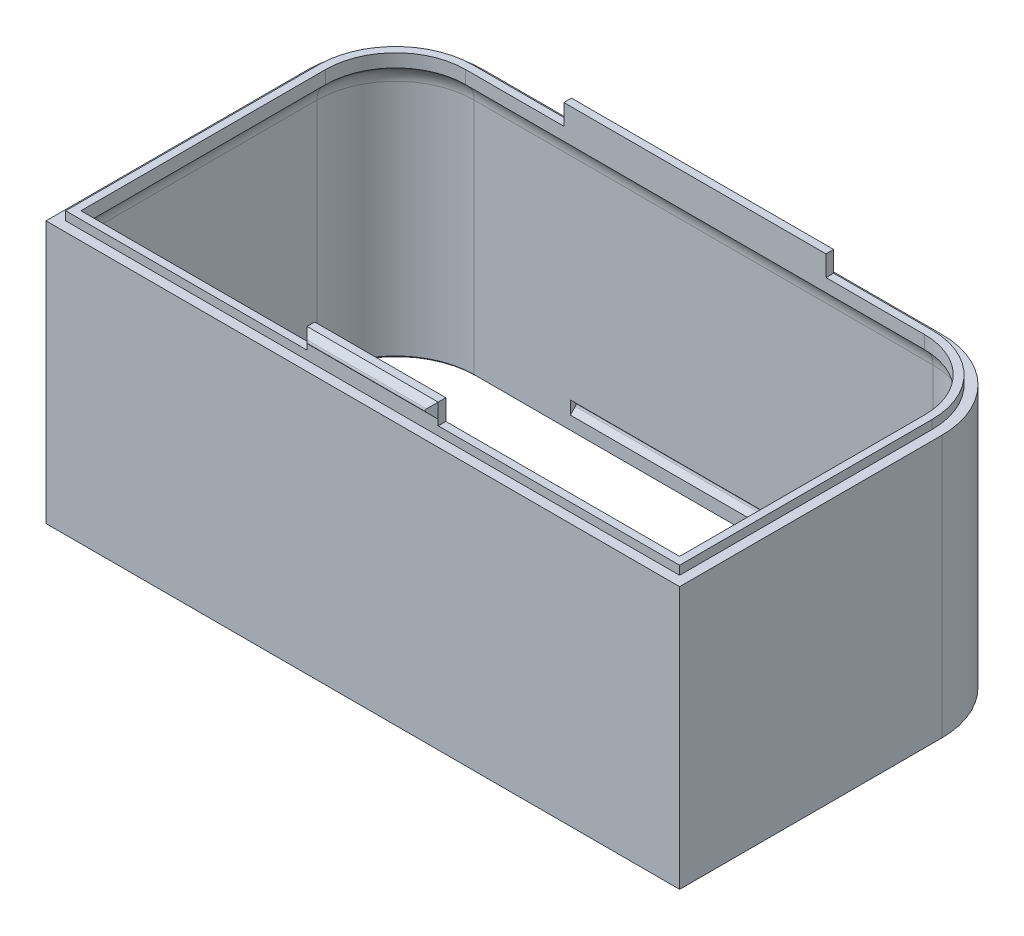
SolidWorks part; units mm, degrees
material "ПК/АБС"
ref_plane "Спереди" through (0, 0, 0) normal (0, 0, 1) x (1, 0, 0)
ref_plane "Сверху" through (0, 0, 0) normal (0, 1, 0) x (1, 0, 0)
ref_plane "Справа" through (0, 0, 0) normal (1, 0, 0) x (0, 0, -1)
sketch "Эскиз1" plane through (0, 0, 0) normal (0, 1, 0) x (1, 0, 0)
  line L0 (-70.5, 2) -> (70.5, 2)
  line L1 (-72.5, 0) -> (72.5, 0)
  line L2 (-72.5, 0) -> (-72.5, 60)
  line L3 (-52.5, 80) -> (52.5, 80)
  line L4 (72.5, 0) -> (72.5, 60)
  line L9 (70.5, 2) -> (70.5, 60)
  line L10 (-52.5, 78) -> (52.5, 78)
  line L11 (-70.5, 2) -> (-70.5, 60)
  arc A0 (72.5, 60) -> (52.5, 80) centre (52.5, 60) ccw
  arc A1 (-52.5, 80) -> (-72.5, 60) centre (-52.5, 60) ccw
  arc A2 (70.5, 60) -> (52.5, 78) centre (52.5, 60) ccw
  arc A3 (-52.5, 78) -> (-70.5, 60) centre (-52.5, 60) ccw
  point P8 (72.5, 80)
  point P11 (-72.5, 80)
  dimension "D3" = 20
  dimension "D1" = 80
  dimension "D2" = 145
  dimension "D4" = 2
extrude "Бобышка-Вытянуть1" add sketch "Эскиз1" along normal blind 60
sketch "Эскиз2" plane through (0, 60, 0) normal (0, 1, 0) x (1, 0, 0)
  line L0 (-68.5, 60) -> (-68.5, 4)
  line L1 (-68.5, 4) -> (68.5, 4)
  line L2 (68.5, 4) -> (68.5, 60)
  line L3 (52.5, 76) -> (-52.5, 76)
  line L4 (-72.5, 60) -> (-72.5, 0)
  line L5 (-72.5, 0) -> (72.5, 0)
  line L6 (72.5, 0) -> (72.5, 60)
  line L7 (52.5, 80) -> (-52.5, 80)
  line L8 (-72.5, 60) -> (-72.5, 0)
  line L9 (-72.5, 0) -> (72.5, 0)
  line L10 (72.5, 0) -> (72.5, 60)
  line L11 (52.5, 80) -> (-52.5, 80)
  arc A0 (68.5, 60) -> (52.5, 76) centre (52.5, 60) ccw
  arc A1 (-52.5, 76) -> (-68.5, 60) centre (-52.5, 60) ccw
  arc A2 (72.5, 60) -> (52.5, 80) centre (52.5, 60) ccw
  arc A3 (-52.5, 80) -> (-72.5, 60) centre (-52.5, 60) ccw
  arc A4 (72.5, 60) -> (52.5, 80) centre (52.5, 60) ccw
  arc A5 (-52.5, 80) -> (-72.5, 60) centre (-52.5, 60) ccw
  dimension "D1" = 0
  dimension "D2" = 4
extrude "Бобышка-Вытянуть2" add sketch "Эскиз2" against normal blind 1
chamfer "Фаска3" distance 2 angle 45 6 edges at (70.5, 59, -31) (65.2279, 59, -72.7279) (0, 59, -78) (-65.2279, 59, -72.7279) (0, 59, -2) (-70.5, 59, -31)
sketch "Эскиз11" plane through (0, 60, 0) normal (0, 1, 0) x (1, 0, 0)
  line L0 (68.5, 4) -> (68.5, 60) construction
  line L1 (-68.5, 4) -> (68.5, 4) construction
  line L2 (-68.5, 60) -> (-68.5, 4) construction
  line L3 (52.5, 76) -> (-52.5, 76) construction
  line L4 (68.5, 4) -> (68.5, 60)
  line L5 (-68.5, 4) -> (68.5, 4)
  line L6 (-68.5, 60) -> (-68.5, 4)
  line L7 (52.5, 76) -> (-52.5, 76)
  line L8 (70.25, 2.25) -> (70.25, 60)
  line L9 (52.5, 77.75) -> (-52.5, 77.75)
  line L10 (-70.25, 60) -> (-70.25, 2.25)
  line L11 (-70.25, 2.25) -> (70.25, 2.25)
  arc A0 (68.5, 60) -> (52.5, 76) centre (52.5, 60) ccw construction
  arc A1 (-52.5, 76) -> (-68.5, 60) centre (-52.5, 60) ccw construction
  arc A2 (68.5, 60) -> (52.5, 76) centre (52.5, 60) ccw
  arc A3 (-52.5, 76) -> (-68.5, 60) centre (-52.5, 60) ccw
  arc A4 (70.25, 60) -> (52.5, 77.75) centre (52.5, 60) ccw
  arc A5 (-52.5, 77.75) -> (-70.25, 60) centre (-52.5, 60) ccw
  dimension "D1" = 1.75
extrude "Бобышка-Вытянуть8" add sketch "Эскиз11" along normal blind 2
sketch "Эскиз12" plane through (0, 0, 0) normal (1, 0, 0) x (0, 0, -1)
  line L0 (76, 59) -> (76, 62) construction
  line L1 (76, 59) -> (76, 62) construction
  line L2 (76, 62) -> (76, 66.7)
  line L3 (76, 66.7) -> (77.75, 66.7)
  line L4 (77.75, 66.7) -> (79.45, 65)
  line L5 (79.45, 65) -> (77.75, 63.3)
  line L6 (77.75, 63.3) -> (77.75, 62)
  line L7 (77.75, 62) -> (76, 62)
  line L9 (80, 60) -> (60, 60) construction
  dimension "D1" = 1.7
  dimension "D2" = 5
extrude "Бобышка-Вытянуть9" add sketch "Эскиз12" along normal mid plane 60
sketch "Эскиз13" plane through (0, 0, 0) normal (1, 0, 0) x (0, 0, -1)
  line L0 (2.25, 62) -> (2.25, 63.3)
  line L1 (2.25, 63.3) -> (0.55, 65)
  line L2 (0.55, 65) -> (2.25, 66.7)
  line L3 (2.25, 66.7) -> (4, 66.7)
  line L4 (4, 66.7) -> (4, 62)
  line L5 (2.25, 62) -> (60, 62) construction
  line L6 (4, 62) -> (2.25, 62)
  line L7 (4, 59) -> (4, 62) construction
  line L8 (4, 59) -> (4, 62) construction
  line L9 (0, 60) -> (60, 60) construction
  dimension "D1" = 5
  dimension "D2" = 1.7
extrude "Бобышка-Вытянуть10" add sketch "Эскиз13" along normal mid plane 30
sketch "Эскиз15" plane through (0, 0, 0) normal (1, 0, 0) x (0, 0, -1)
  line L0 (2, 3.5) -> (2, 6.5)
  line L1 (2, 6.5) -> (0.5, 5)
  line L2 (0.5, 5) -> (2, 3.5)
  line L3 (0, 60) -> (0, 0) construction
  line L4 (0, 0) -> (60, 0) construction
  dimension "D1" = 2
  dimension "D2" = 1.5
  dimension "D3" = 5
extrude "Вырез-Вытянуть2" cut sketch "Эскиз15" against normal mid plane 31
sketch "Эскиз16" plane through (0, 0, 0) normal (1, 0, 0) x (0, 0, -1)
  line L0 (78, 3.5) -> (78, 6.5)
  line L1 (78, 6.5) -> (79.5, 5)
  line L2 (79.5, 5) -> (78, 3.5)
  line L3 (60, 0) -> (80, 0) construction
  dimension "D1" = 2
  dimension "D2" = 1.5
  dimension "D3" = 5
extrude "Вырез-Вытянуть3" cut sketch "Эскиз16" against normal mid plane 61
chamfer "Фаска6" distance 0.5 angle 45 6 edges at (-70.5, 0, -31) (-65.2279, 0, -72.7279) (0, 0, -78) (65.2279, 0, -72.7279) (0, 0, -2) (70.5, 0, -31)
fillet "Скругление3" radius 5 6 edges at (70.5, 57, -31) (65.2279, 57, -72.7279) (0, 57, -78) (-65.2279, 57, -72.7279) (0, 57, -2) (-70.5, 57, -31)
fillet "Скругление4" radius 0.5 2 edges at (0, 5, -0.5) (0, 5, -79.5)
fillet "Скругление5" radius 0.5 2 edges at (0, 65, -79.45) (0, 65, -0.55)
sketch "Эскиз18" plane through (0, 0, 0) normal (0, 0, 1) x (1, 0, 0)
  line L0 (-72.5, 0) -> (72.5, 0) construction
  line L1 (-11, 30) -> (-10, 30)
  line L2 (-11, 30) -> (-11, 0)
  line L3 (-11, 0) -> (-10, 0)
  line L4 (-10, 30) -> (-10, 0)
  line L5 (-10, 30) -> (10, 30) construction
  line L6 (10, 30) -> (11, 30)
  line L7 (10, 30) -> (10, 0)
  line L8 (10, 0) -> (11, 0)
  line L9 (11, 30) -> (11, 0)
  line L10 (0, 0) -> (0, 30) construction
  dimension "D1" = 20
  dimension "D2" = 1
  dimension "D3" = 30
extrude "Вырез-Вытянуть4" [suppressed] cut sketch "Эскиз18" against normal up to surface (2 mm away) up to face at (0, 5, -2)
sketch "Эскиз19" plane through (0, 62, 0) normal (0, 1, 0) x (1, 0, 0)
  line L0 (30, 77.75) -> (28, 79.75)
  line L2 (28, 79.75) -> (30, 79.75)
  line L4 (30, 79.75) -> (30, 77.75)
  line L5 (-30, 77.75) -> (-28, 79.75)
  line L6 (-28, 79.75) -> (-30, 79.75)
  line L7 (-30, 79.75) -> (-30, 77.75)
  line L8 (-15, 2.25) -> (-13, 0.25)
  line L9 (-13, 0.25) -> (-15, 0.25)
  line L10 (-15, 0.25) -> (-15, 2.25)
  line L11 (15, 2.25) -> (15, 0.25)
  line L12 (15, 0.25) -> (13, 0.25)
  line L13 (13, 0.25) -> (15, 2.25)
  point P3 (29.517, 79.6125)
  point P4 (30, 77.75)
  point P7 (-30, 79.2429)
  point P8 (27.5789, 77.75)
  point P19 (15, 0.7571)
  point P21 (30, 77.75)
  point P23 (29.179, 79.2429)
  point P24 (30, 77.75)
  point P26 (31.1258, 79.2429)
  point P27 (30.4846, 79.2429)
  dimension "D1" = 2
extrude "Вырез-Вытянуть5" cut sketch "Эскиз19" along normal through all
